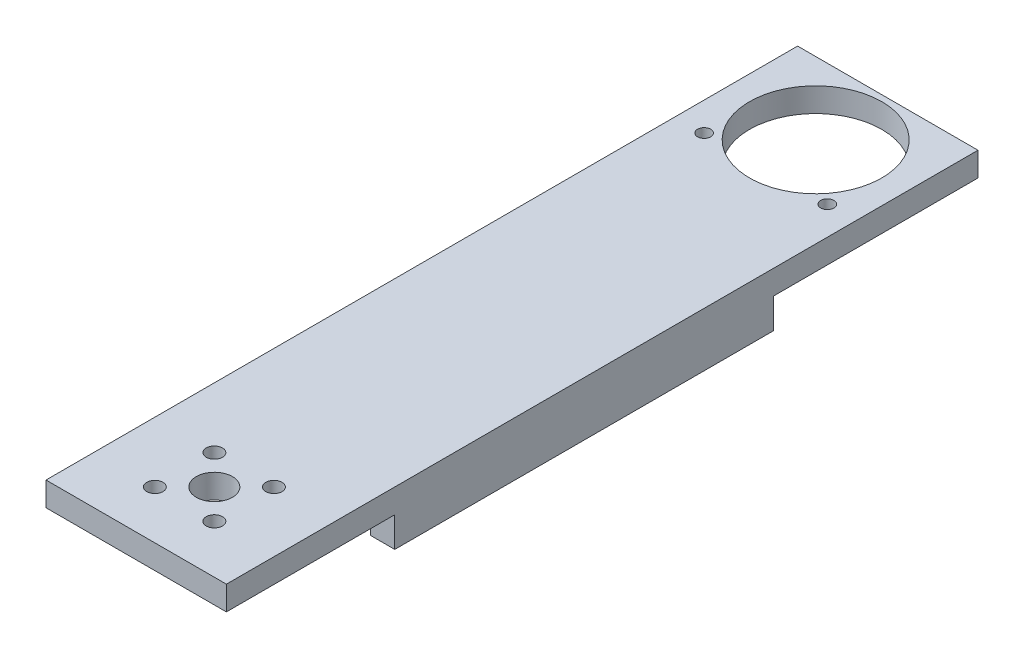
SolidWorks part; units mm, degrees
ref_plane "Front Plane" through (0, 0, 0) normal (0, 0, 1) x (1, 0, 0)
ref_plane "Top Plane" through (0, 0, 0) normal (0, 1, 0) x (1, 0, 0)
ref_plane "Right Plane" through (0, 0, 0) normal (1, 0, 0) x (0, 0, -1)
ref_plane "PZ_m112_000" through (0, 0, -112) normal (0, 0, 1) x (1, 0, 0)
sketch "S_box1" plane through (0, 0, -112) normal (0, 0, 1) x (1, 0, 0)
  line L0 (-15, -20) -> (15, -20)
  line L1 (15, -20) -> (15, -16)
  line L2 (15, -16) -> (-15, -16)
  line L3 (-15, -16) -> (-15, -20)
  dimension "P1" = 15
  dimension "P2" = 20
  dimension "P3" = 15
  dimension "P4" = 20
  dimension "P5" = 15
  dimension "P6" = 16
  dimension "P7" = 15
  dimension "P8" = 16
extrude "Boss_1" add sketch "S_box1" along normal blind 125
ref_plane "PZ_m78_000" through (0, 0, -78) normal (0, 0, 1) x (1, 0, 0)
sketch "S_box2" plane through (0, 0, -78) normal (0, 0, 1) x (1, 0, 0)
  line L0 (-15, -25) -> (-11, -25)
  line L1 (-11, -25) -> (-11, -19.5)
  line L2 (-11, -19.5) -> (-15, -19.5)
  line L3 (-15, -19.5) -> (-15, -25)
  dimension "P1" = 15
  dimension "P2" = 25
  dimension "P3" = 11
  dimension "P4" = 25
  dimension "P5" = 11
  dimension "P6" = 19.5
  dimension "P7" = 15
  dimension "P8" = 19.5
extrude "Boss_2" add sketch "S_box2" along normal blind 63
sketch "S_box3" plane through (0, 0, -78) normal (0, 0, 1) x (1, 0, 0)
  line L0 (11, -25) -> (15, -25)
  line L1 (15, -25) -> (15, -19.5)
  line L2 (15, -19.5) -> (11, -19.5)
  line L3 (11, -19.5) -> (11, -25)
  dimension "P1" = 11
  dimension "P2" = 25
  dimension "P3" = 15
  dimension "P4" = 25
  dimension "P5" = 15
  dimension "P6" = 19.5
  dimension "P7" = 11
  dimension "P8" = 19.5
extrude "Boss_3" add sketch "S_box3" along normal blind 63
ref_plane "PY_m20_100" through (0, -20.1, 0) normal (0, 1, 0) x (1, 0, 0)
sketch "S_hole4" plane through (0, -20.1, 0) normal (0, 1, 0) x (1, 0, 0)
  circle A0 centre (0, 0) radius 3
  dimension "D1_S_hole4" = 6
extrude "Hole_4" cut sketch "S_hole4" along normal blind 4.2
sketch "S_hole5" plane through (0, -20.1, 0) normal (0, 1, 0) x (1, 0, 0)
  circle A0 centre (4.9497, -4.9497) radius 1.35
  dimension "D1_S_hole5" = 2.7
  dimension "P2" = 4.9497
  dimension "P3" = 4.9497
extrude "Hole_5" cut sketch "S_hole5" along normal blind 4.2
sketch "S_hole6" plane through (0, -20.1, 0) normal (0, 1, 0) x (1, 0, 0)
  circle A0 centre (-4.9497, -4.9497) radius 1.35
  dimension "D1_S_hole6" = 2.7
  dimension "P2" = 4.9497
  dimension "P3" = 4.9497
extrude "Hole_6" cut sketch "S_hole6" along normal blind 4.2
sketch "S_hole7" plane through (0, -20.1, 0) normal (0, 1, 0) x (1, 0, 0)
  circle A0 centre (-4.9497, 4.9497) radius 1.35
  dimension "D1_S_hole7" = 2.7
  dimension "P2" = 4.9497
  dimension "P3" = 4.9497
extrude "Hole_7" cut sketch "S_hole7" along normal blind 4.2
sketch "S_hole8" plane through (0, -20.1, 0) normal (0, 1, 0) x (1, 0, 0)
  circle A0 centre (4.9497, 4.9497) radius 1.35
  dimension "D1_S_hole8" = 2.7
  dimension "P2" = 4.9497
  dimension "P3" = 4.9497
extrude "Hole_8" cut sketch "S_hole8" along normal blind 4.2
sketch "S_hole9" plane through (0, -20.1, 0) normal (0, 1, 0) x (1, 0, 0)
  circle A0 centre (0, 100) radius 11
  dimension "D1_S_hole9" = 22
  dimension "P2" = 100
extrude "Hole_9" cut sketch "S_hole9" along normal blind 4.2
sketch "S_hole10" plane through (0, -20.1, 0) normal (0, 1, 0) x (1, 0, 0)
  circle A0 centre (-10.25, 91.7) radius 1.1
  dimension "D1_S_hole10" = 2.2
  dimension "P2" = 10.25
  dimension "P3" = 91.7
extrude "Hole_10" cut sketch "S_hole10" along normal blind 4.2
sketch "S_hole11" plane through (0, -20.1, 0) normal (0, 1, 0) x (1, 0, 0)
  circle A0 centre (10.25, 91.7) radius 1.1
  dimension "D1_S_hole11" = 2.2
  dimension "P2" = 10.25
  dimension "P3" = 91.7
extrude "Hole_11" cut sketch "S_hole11" along normal blind 4.2
sketch "S_hole12" plane through (0, -20.1, 0) normal (0, 1, 0) x (1, 0, 0)
  circle A0 centre (-10.25, 67.25) radius 1.1
  dimension "D1_S_hole12" = 2.2
  dimension "P2" = 10.25
  dimension "P3" = 67.25
extrude "Hole_12" cut sketch "S_hole12" against normal blind 4.2
sketch "S_hole13" plane through (0, -20.1, 0) normal (0, 1, 0) x (1, 0, 0)
  circle A0 centre (10.25, 67.25) radius 1.1
  dimension "D1_S_hole13" = 2.2
  dimension "P2" = 10.25
  dimension "P3" = 67.25
extrude "Hole_13" cut sketch "S_hole13" against normal blind 4.2
equation "\"plate_t\" = 3"
equation "\"clearance\" = 0.4"
